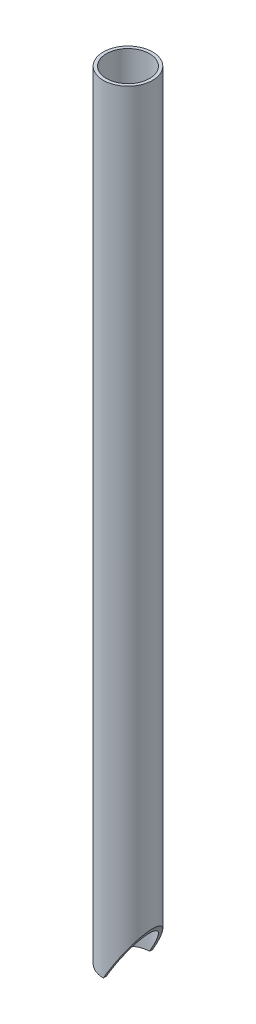
SolidWorks part; units mm, degrees
ref_plane "Front Plane" through (0, 0, 0) normal (0, 0, 1) x (1, 0, 0)
ref_plane "Top Plane" through (0, 0, 0) normal (0, 1, 0) x (1, 0, 0)
ref_plane "Right Plane" through (0, 0, 0) normal (1, 0, 0) x (0, 0, -1)
sketch "Sketch1" plane through (0, 0, 0) normal (0, 1, 0) x (1, 0, 0)
  circle A0 centre (0, 0) radius 8
  circle A1 centre (0, 0) radius 7
  dimension "D1" = 16
  dimension "D2" = 14
extrude "Boss-Extrude1" add sketch "Sketch1" along normal blind 252.432
sketch "Sketch2" plane through (0, 0, 0) normal (0, 0, 1) x (1, 0, 0)
  line L0 (0, 0) -> (8, 13.8564)
  line L1 (8, 0) -> (8, 252.432) construction
  line L2 (-8, 0) -> (8, 0) construction
  line L3 (0, 0) -> (8, 0)
  line L4 (8, 0) -> (8, 13.8564)
  dimension "D1" = 60
extrude "Cut-Extrude1" cut sketch "Sketch2" against normal blind 272.58 and the other way blind 272.58
equation "\"D1@Boss-Extrude1\"=(150*cos(45)+20.15)/cos(60)"
